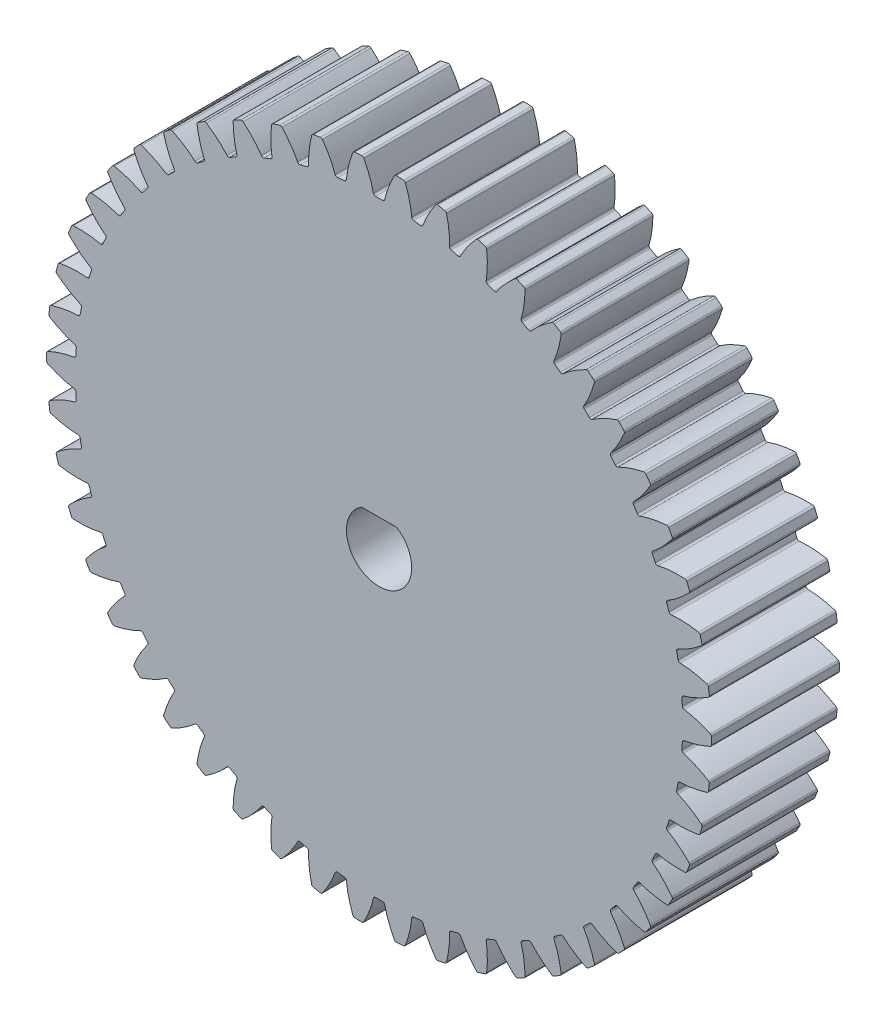
SolidWorks part; units mm, degrees
material "Alloy Steel"
ref_plane "Front" through (0, 0, 0) normal (0, 0, 1) x (1, 0, 0)
ref_plane "Top" through (0, 0, 0) normal (0, 1, 0) x (1, 0, 0)
ref_plane "Right" through (0, 0, 0) normal (1, 0, 0) x (0, 0, -1)
sketch "Sketch1" plane through (0, 0, 0) normal (0, 0, 1) x (1, 0, 0)
  circle A0 centre (0, 0) radius 26
  dimension "OutsideDiameter" = 52
extrude "Boss-Extrude1" add sketch "Sketch1" along normal blind 10
sketch "Sketch3" plane through (0, 0, 0) normal (0, 0, 1) x (1, 0, 0)
  line L0 (0, 0) -> (43.7181, 0) construction
  line L2 (0, 0) -> (-0.3921, 23.7468) construction
  line L3 (0, 0) -> (0.3921, 23.7468) construction
  line L4 (0.3921, 23.7468) -> (0.3879, 23.4891) construction
  line L5 (0, 0) -> (0, 61.276) construction
  line L6 (-0.3921, 23.7468) -> (-0.3879, 23.4891) construction
  circle A0 centre (0, 0) radius 26 construction
  circle A1 centre (0, 0) radius 25 construction
  circle A2 centre (0, 0) radius 23.4923 construction
  arc A3 (0.3921, 23.7468) -> (-0.3921, 23.7468) centre (0, 0) ccw construction
  arc A5 (1.2454, 25.9702) -> (-1.2454, 25.9702) centre (0, 0) ccw
  spline S0 degree 4 poles (-0.3879, 23.4891) (-0.388, 23.493) (-0.3884, 23.504) (-0.3897, 23.5247) (-0.3924, 23.5584) (-0.3969, 23.6014) (-0.4038, 23.6569) (-0.4135, 23.7223) (-0.4257, 23.7941) (-0.4406, 23.8721) (-0.4569, 23.9499) (-0.4746, 24.0275) (-0.4935, 24.1047) (-0.5179, 24.1981) (-0.5491, 24.3101) (-0.5886, 24.4407) (-0.6369, 24.5888) (-0.6899, 24.7394) (-0.7452, 24.8875) (-0.8046, 25.0368) (-0.8646, 25.1811) (-0.9305, 25.3308) (-0.9933, 25.4688) (-1.0677, 25.6231) (-1.1289, 25.7476) (-1.2139, 25.9114) (-1.2654, 26.008) (-1.3272, 26.121) (-1.3555, 26.1712) (-1.3728, 26.202) knots 0 0 0 0 0 0.005377 0.015084 0.028532 0.04661 0.064855 0.092111 0.119476 0.146842 0.174209 0.201575 0.228941 0.256307 0.307035 0.361767 0.4165 0.471232 0.525964 0.580697 0.635429 0.690161 0.744894 0.799626 0.854358 0.909091 0.954545 1 1 1 1 1 construction
  spline S1 degree 4 poles (-0.3879, 23.4891) (-0.388, 23.493) (-0.3884, 23.504) (-0.3897, 23.5247) (-0.3924, 23.5584) (-0.3969, 23.6014) (-0.4038, 23.6569) (-0.4135, 23.7223) (-0.4257, 23.7941) (-0.4406, 23.8721) (-0.4569, 23.9499) (-0.4746, 24.0275) (-0.4935, 24.1047) (-0.5179, 24.1981) (-0.5491, 24.3101) (-0.5886, 24.4407) (-0.6369, 24.5888) (-0.6899, 24.7394) (-0.7452, 24.8875) (-0.8046, 25.0368) (-0.8646, 25.1811) (-0.9305, 25.3308) (-0.9933, 25.4688) (-1.0677, 25.6231) (-1.1289, 25.7476) (-1.1955, 25.8759) (-1.2284, 25.9383) (-1.2454, 25.9702) knots 0 0 0 0 0 0.005377 0.015084 0.028532 0.04661 0.064855 0.092111 0.119476 0.146842 0.174209 0.201575 0.228941 0.256307 0.307035 0.361767 0.4165 0.471232 0.525964 0.580697 0.635429 0.690161 0.744894 0.799626 0.854358 0.909091 0.909091 0.909091 0.909091 0.909091
  spline S2 degree 4 poles (0.3879, 23.4891) (0.388, 23.493) (0.3884, 23.504) (0.3897, 23.5247) (0.3924, 23.5584) (0.3969, 23.6014) (0.4038, 23.6569) (0.4135, 23.7223) (0.4257, 23.7941) (0.4406, 23.8721) (0.4569, 23.9499) (0.4746, 24.0275) (0.4935, 24.1047) (0.5179, 24.1981) (0.5491, 24.3101) (0.5886, 24.4407) (0.6369, 24.5888) (0.6899, 24.7394) (0.7452, 24.8875) (0.8046, 25.0368) (0.8646, 25.1811) (0.9305, 25.3308) (0.9933, 25.4688) (1.0677, 25.6231) (1.1289, 25.7476) (1.2139, 25.9114) (1.2654, 26.008) (1.3272, 26.121) (1.3555, 26.1712) (1.3728, 26.202) knots 0 0 0 0 0 0.005377 0.015084 0.028532 0.04661 0.064855 0.092111 0.119476 0.146842 0.174209 0.201575 0.228941 0.256307 0.307035 0.361767 0.4165 0.471232 0.525964 0.580697 0.635429 0.690161 0.744894 0.799626 0.854358 0.909091 0.954545 1 1 1 1 1 construction
  spline S3 degree 4 poles (0.3879, 23.4891) (0.388, 23.493) (0.3884, 23.504) (0.3897, 23.5247) (0.3924, 23.5584) (0.3969, 23.6014) (0.4038, 23.6569) (0.4135, 23.7223) (0.4257, 23.7941) (0.4406, 23.8721) (0.4569, 23.9499) (0.4746, 24.0275) (0.4935, 24.1047) (0.5179, 24.1981) (0.5491, 24.3101) (0.5886, 24.4407) (0.6369, 24.5888) (0.6899, 24.7394) (0.7452, 24.8875) (0.8046, 25.0368) (0.8646, 25.1811) (0.9305, 25.3308) (0.9933, 25.4688) (1.0677, 25.6231) (1.1289, 25.7476) (1.1955, 25.8759) (1.2284, 25.9383) (1.2454, 25.9702) knots 0 0 0 0 0 0.005377 0.015084 0.028532 0.04661 0.064855 0.092111 0.119476 0.146842 0.174209 0.201575 0.228941 0.256307 0.307035 0.361767 0.4165 0.471232 0.525964 0.580697 0.635429 0.690161 0.744894 0.799626 0.854358 0.909091 0.909091 0.909091 0.909091 0.909091
  point P0 (0, 23.75)
  dimension "OutsideDiameter" = 52
  dimension "PitchCircle" = 50
  dimension "BaseCircle" = 46.9846
  dimension "DedendumCircle" = 47.5
sketch "DCLTBC" [suppressed] plane through (0, 0, 0) normal (0, 0, 1) x (1, 0, 0)
  line L0 (0, 0) -> (41.04, 0) construction
  line L1 (-0.539, 11.2371) -> (-0.5627, 11.7327) construction
  line L2 (0.539, 11.2371) -> (0.5627, 11.7327) construction
  line L3 (-0.539, 11.2371) -> (-0.5627, 11.7327)
  line L4 (0.539, 11.2371) -> (0.5627, 11.7327)
  line L5 (0, 0) -> (0, 104.9356) construction
  circle A0 centre (0, 0) radius 13.5
  circle A1 centre (0, 0) radius 12.5 construction
  circle A2 centre (0, 0) radius 11.7462 construction
  arc A3 (0.539, 11.2371) -> (-0.539, 11.2371) centre (0, 0) ccw construction
  arc A4 (0.539, 11.2371) -> (-0.539, 11.2371) centre (0, 0) ccw
  spline S0 degree 4 poles (-1995.7925, -124.0386) (-18.637, 9.6549) (-0.7482, 10.902) (-0.5144, 11.3546) (-0.568, 11.7819) (-0.5727, 11.8124) (-0.5797, 11.8517) (-0.5892, 11.8979) (-0.601, 11.9485) (-0.6152, 12.0034) (-0.6307, 12.0579) (-0.6473, 12.1122) (-0.6648, 12.1662) (-0.6873, 12.2313) (-0.716, 12.3091) (-0.752, 12.3996) (-0.7958, 12.5017) (-0.8436, 12.6052) (-0.8931, 12.7065) (-0.9461, 12.8082) (-0.9995, 12.9061) (-1.0579, 13.0071) (-1.1133, 13.1) (-1.1787, 13.2033) (-1.5156, 13.7241) (-2.9947, 15.6922) (22.2491, -20.3107) (-1154.5903, 1647.3833) knots -0.784355 -0.784355 -0.784355 -0.784355 -0.784355 0.005377 0.015084 0.028532 0.04661 0.064855 0.092111 0.119476 0.146842 0.174209 0.201575 0.228941 0.256307 0.307035 0.361767 0.4165 0.471232 0.525964 0.580697 0.635429 0.690161 0.744894 0.799626 0.854358 2.062408 2.062408 2.062408 2.062408 2.062408 only from (-0.5627, 11.7327) to (-1.3344, 13.4339) construction
  spline S1 degree 4 poles (1995.7925, -124.0386) (18.637, 9.6549) (0.7482, 10.902) (0.5144, 11.3546) (0.568, 11.7819) (0.5727, 11.8124) (0.5797, 11.8517) (0.5892, 11.8979) (0.601, 11.9485) (0.6152, 12.0034) (0.6307, 12.0579) (0.6473, 12.1122) (0.6648, 12.1662) (0.6873, 12.2313) (0.716, 12.3091) (0.752, 12.3996) (0.7958, 12.5017) (0.8436, 12.6052) (0.8931, 12.7065) (0.9461, 12.8082) (0.9995, 12.9061) (1.0579, 13.0071) (1.1133, 13.1) (1.1787, 13.2033) (1.5156, 13.7241) (2.9947, 15.6922) (-22.2491, -20.3107) (1154.5903, 1647.3833) knots -0.784355 -0.784355 -0.784355 -0.784355 -0.784355 0.005377 0.015084 0.028532 0.04661 0.064855 0.092111 0.119476 0.146842 0.174209 0.201575 0.228941 0.256307 0.307035 0.361767 0.4165 0.471232 0.525964 0.580697 0.635429 0.690161 0.744894 0.799626 0.854358 2.062408 2.062408 2.062408 2.062408 2.062408 only from (0.5627, 11.7327) to (1.3344, 13.4339) construction
  spline S2 degree 4 poles (-0.5627, 11.7327) (-0.5629, 11.7355) (-0.5635, 11.7432) (-0.565, 11.758) (-0.568, 11.7819) (-0.5727, 11.8124) (-0.5797, 11.8517) (-0.5892, 11.8979) (-0.601, 11.9485) (-0.6152, 12.0034) (-0.6307, 12.0579) (-0.6473, 12.1122) (-0.6648, 12.1662) (-0.6873, 12.2313) (-0.716, 12.3091) (-0.752, 12.3996) (-0.7958, 12.5017) (-0.8436, 12.6052) (-0.8931, 12.7065) (-0.9461, 12.8082) (-0.9995, 12.9061) (-1.0579, 13.0071) (-1.1133, 13.1) (-1.1787, 13.2033) (-1.2325, 13.2864) (-1.2907, 13.3715) (-1.3195, 13.4128) (-1.3344, 13.4339) knots 0 0 0 0 0 0.005377 0.015084 0.028532 0.04661 0.064855 0.092111 0.119476 0.146842 0.174209 0.201575 0.228941 0.256307 0.307035 0.361767 0.4165 0.471232 0.525964 0.580697 0.635429 0.690161 0.744894 0.799626 0.854358 0.909091 0.909091 0.909091 0.909091 0.909091
  spline S3 degree 4 poles (0.5627, 11.7327) (0.5629, 11.7355) (0.5635, 11.7432) (0.565, 11.758) (0.568, 11.7819) (0.5727, 11.8124) (0.5797, 11.8517) (0.5892, 11.8979) (0.601, 11.9485) (0.6152, 12.0034) (0.6307, 12.0579) (0.6473, 12.1122) (0.6648, 12.1662) (0.6873, 12.2313) (0.716, 12.3091) (0.752, 12.3996) (0.7958, 12.5017) (0.8436, 12.6052) (0.8931, 12.7065) (0.9461, 12.8082) (0.9995, 12.9061) (1.0579, 13.0071) (1.1133, 13.1) (1.1787, 13.2033) (1.2325, 13.2864) (1.2907, 13.3715) (1.3195, 13.4128) (1.3344, 13.4339) knots 0 0 0 0 0 0.005377 0.015084 0.028532 0.04661 0.064855 0.092111 0.119476 0.146842 0.174209 0.201575 0.228941 0.256307 0.307035 0.361767 0.4165 0.471232 0.525964 0.580697 0.635429 0.690161 0.744894 0.799626 0.854358 0.909091 0.909091 0.909091 0.909091 0.909091
  dimension "OutsideDiameter" = 52
  dimension "PitchCircle" = 50
  dimension "BaseCircle" = 46.9846
extrude "Cut-Extrude-DCLTBC" [suppressed] cut sketch "DCLTBC" along normal through all
fillet "Fillet-Tip-DCLTBC" [suppressed] radius 0.1678
fillet "Fillet-Root-DCLTBC" [suppressed] radius 0.3355
pattern_circular "CirPattern-DCLTBC" [suppressed] count 50 over 360 of bodies 111
sketch "DCGTBC" plane through (0, 0, 0) normal (0, 0, 1) x (1, 0, 0)
  line L0 (0, 0) -> (41.04, 0) construction
  line L1 (-23.6596, 2.0699) -> (0, 0) construction
  line L2 (0, 0) -> (23.6596, 2.0699) construction
  line L3 (0, 0) -> (-16.5124, 0)
  line L5 (0, 0) -> (0, 104.9356) construction
  circle A0 centre (0, 0) radius 26
  circle A1 centre (0, 0) radius 25 construction
  circle A2 centre (0, 0) radius 23.4923 construction
  arc A3 (0.3921, 23.7468) -> (-0.3921, 23.7468) centre (0, 0) ccw construction
  arc A11 (23.6596, 2.0699) -> (-23.6596, 2.0699) centre (0, 0) ccw
  spline S4 degree 4 poles (999.4864, -18.7848) (11.7157, 21.9438) (0.5361, 22.5725) (0.3526, 23.0676) (0.3924, 23.5584) (0.3969, 23.6014) (0.4038, 23.6569) (0.4135, 23.7223) (0.4257, 23.7941) (0.4406, 23.8721) (0.4569, 23.9499) (0.4746, 24.0275) (0.4935, 24.1047) (0.5179, 24.1981) (0.5491, 24.3101) (0.5886, 24.4407) (0.6369, 24.5888) (0.6899, 24.7394) (0.7452, 24.8875) (0.8046, 25.0368) (0.8646, 25.1811) (0.9305, 25.3308) (0.9933, 25.4688) (1.0677, 25.6231) (1.3761, 26.2503) (2.5138, 28.2725) (-11.1356, 2.527) (472.7395, 907.8123) knots -0.631302 -0.631302 -0.631302 -0.631302 -0.631302 0.005377 0.015084 0.028532 0.04661 0.064855 0.092111 0.119476 0.146842 0.174209 0.201575 0.228941 0.256307 0.307035 0.361767 0.4165 0.471232 0.525964 0.580697 0.635429 0.690161 0.744894 0.799626 0.854358 1.793522 1.793522 1.793522 1.793522 1.793522 only from (0.3879, 23.4891) to (1.2454, 25.9702) construction
  spline S5 degree 4 poles (-999.4864, -18.7848) (-11.7157, 21.9438) (-0.5361, 22.5725) (-0.3526, 23.0676) (-0.3924, 23.5584) (-0.3969, 23.6014) (-0.4038, 23.6569) (-0.4135, 23.7223) (-0.4257, 23.7941) (-0.4406, 23.8721) (-0.4569, 23.9499) (-0.4746, 24.0275) (-0.4935, 24.1047) (-0.5179, 24.1981) (-0.5491, 24.3101) (-0.5886, 24.4407) (-0.6369, 24.5888) (-0.6899, 24.7394) (-0.7452, 24.8875) (-0.8046, 25.0368) (-0.8646, 25.1811) (-0.9305, 25.3308) (-0.9933, 25.4688) (-1.0677, 25.6231) (-1.3761, 26.2503) (-2.5138, 28.2725) (11.1356, 2.527) (-472.7395, 907.8123) knots -0.631302 -0.631302 -0.631302 -0.631302 -0.631302 0.005377 0.015084 0.028532 0.04661 0.064855 0.092111 0.119476 0.146842 0.174209 0.201575 0.228941 0.256307 0.307035 0.361767 0.4165 0.471232 0.525964 0.580697 0.635429 0.690161 0.744894 0.799626 0.854358 1.793522 1.793522 1.793522 1.793522 1.793522 only from (-0.3879, 23.4891) to (-1.2454, 25.9702) construction
  spline S6 degree 4 poles (0.3879, 23.4891) (0.388, 23.493) (0.3884, 23.504) (0.3897, 23.5247) (0.3924, 23.5584) (0.3969, 23.6014) (0.4038, 23.6569) (0.4135, 23.7223) (0.4257, 23.7941) (0.4406, 23.8721) (0.4569, 23.9499) (0.4746, 24.0275) (0.4935, 24.1047) (0.5179, 24.1981) (0.5491, 24.3101) (0.5886, 24.4407) (0.6369, 24.5888) (0.6899, 24.7394) (0.7452, 24.8875) (0.8046, 25.0368) (0.8646, 25.1811) (0.9305, 25.3308) (0.9933, 25.4688) (1.0677, 25.6231) (1.1289, 25.7476) (1.1955, 25.8759) (1.2284, 25.9383) (1.2454, 25.9702) knots 0 0 0 0 0 0.005377 0.015084 0.028532 0.04661 0.064855 0.092111 0.119476 0.146842 0.174209 0.201575 0.228941 0.256307 0.307035 0.361767 0.4165 0.471232 0.525964 0.580697 0.635429 0.690161 0.744894 0.799626 0.854358 0.909091 0.909091 0.909091 0.909091 0.909091
  spline S7 degree 4 poles (-0.3879, 23.4891) (-0.388, 23.493) (-0.3884, 23.504) (-0.3897, 23.5247) (-0.3924, 23.5584) (-0.3969, 23.6014) (-0.4038, 23.6569) (-0.4135, 23.7223) (-0.4257, 23.7941) (-0.4406, 23.8721) (-0.4569, 23.9499) (-0.4746, 24.0275) (-0.4935, 24.1047) (-0.5179, 24.1981) (-0.5491, 24.3101) (-0.5886, 24.4407) (-0.6369, 24.5888) (-0.6899, 24.7394) (-0.7452, 24.8875) (-0.8046, 25.0368) (-0.8646, 25.1811) (-0.9305, 25.3308) (-0.9933, 25.4688) (-1.0677, 25.6231) (-1.1289, 25.7476) (-1.1955, 25.8759) (-1.2284, 25.9383) (-1.2454, 25.9702) knots 0 0 0 0 0 0.005377 0.015084 0.028532 0.04661 0.064855 0.092111 0.119476 0.146842 0.174209 0.201575 0.228941 0.256307 0.307035 0.361767 0.4165 0.471232 0.525964 0.580697 0.635429 0.690161 0.744894 0.799626 0.854358 0.909091 0.909091 0.909091 0.909091 0.909091
  dimension "D1" = 5
  dimension "D2" = 5
  dimension "OutsideDiameter" = 52
  dimension "PitchCircle" = 50
  dimension "BaseCircle" = 46.9846
extrude "Cut-Extrude-DCGTBC" cut sketch "DCGTBC" along normal through all contours A0 A11 region at (0, 25.0744, 0)
fillet "Fillet-Tip-DCGTBC" radius 0.1678 4 edges at (1.2454, 25.9702, 5) (-1.2454, 25.9702, 5) (0.4177, 23.7463, 5) (-0.4177, 23.7463, 5)
pattern_circular "CirPattern-DCGTBC" count 50 over 360 about axis through (0, 0, 10) along (0, 0, 1) of "Cut-Extrude-DCGTBC", "Fillet-Tip-DCGTBC"
sketch "Sketch5" [suppressed] plane through (0, 0, 10) normal (0, 0, 1) x (1, 0, 0)
  circle A0 centre (0, 0) radius 11.25
  arc A1 (0.2133, 11.248) -> (-0.2133, 11.248) centre (0, 0) ccw construction
extrude "Boss-Extrude2" [suppressed] add sketch "Sketch5" along normal blind 7
sketch "Sketch6" plane through (0, 0, 0) normal (0, 0, -1) x (-1, 0, 0)
  line L0 (-1.3711, 2.15) -> (1.3711, 2.15)
  arc A0 (-1.3711, 2.15) -> (1.3711, 2.15) centre (0, 0) ccw
  dimension "D1" = 5.1
  dimension "D2" = 2.15
extrude "Cut-Extrude1" cut sketch "Sketch6" against normal through all both and the other way through all
sketch "Sketch7" plane through (0, 0, 0) normal (0, 0, -1) x (-1, 0, 0)
  circle A0 centre (0, 0) radius 25
  dimension "D1" = 50
sketch "Sketch8" plane through (0, 0, 10) normal (0, 0, 1) x (1, 0, 0)
  circle A0 centre (0, 0) radius 25
  dimension "D1" = 50
equation "\"DiametralPitch\"= 25.4 / 1 'Diametral Pitch"
equation "\"NumTeeth\" = 50'Number of Teeth"
equation "\"PressureAngle\"= 20deg'Pressure Angle"
equation "\"Addendum\"= 1 / \"DiametralPitch\"'Addendum"
equation "\"Dedendum\"= 1.25 / \"DiametralPitch\"'Dedendum"
equation "\"WorkingDepth\"= 2 / \"DiametralPitch\"'Working Depth - here for REF (Not used in building model)"
equation "\"WholeDepth\"= 2.25 / \"DiametralPitch\"'Whole Depth - here for REF (Not used in building model)"
equation "\"Clearance\"= .25 / \"DiametralPitch\"'Clearance"
equation "\"CircularPitch\"= pi / \"DiametralPitch\"'Circular Pitch - here for REF (Not used in building model)"
equation "\"PitchCircle\"= \"NumTeeth\" / \"DiametralPitch\"'Pitch Circle - or - Pitch Diameter"
equation "\"OutsideDiameter\"= ( \"NumTeeth\" + 2 ) / \"DiametralPitch\"'Outside Diameter"
equation "\"Fillet_Root\"= \"Clearance\" * cos ( \"PressureAngle\" ) * tan ( ( 90 + \"PressureAngle\" ) / 2 ) 'Fillet Root"
equation "\"AddendumCircle\"= \"PitchCircle\" + ( 2 * \"Addendum\" )'Addendum Circle - or - Addendum Diameter"
equation "\"DedendumCircle\"= \"PitchCircle\" - ( 2 * \"Dedendum\" )'Dedendum Circle - or - Dedendum Diameter"
equation "\"BaseCircle\"= \"PitchCircle\" * cos ( \"PressureAngle\" )'Base Circle - Base Diameter"
equation "\"PitchAngle\"= 360deg / \"NumTeeth\"'Pitch Angle"
equation "\"Alpha\"= sqr ( \"PitchCircle\" ^ 2 - \"BaseCircle\" ^ 2 ) / \"BaseCircle\" * 180 / PI - \"PressureAngle\"'Alpha - Used for Calculating Beta"
equation "\"Beta\"= ( \"PitchAngle\" / 4 - ( \"Alpha\" - 90 ) )'Beta - Used in definition of the parameters for the parametric equation driven curve"
equation "\"Gamma\"= ( \"PitchAngle\" / 4 - ( \"Alpha\" + 90 ) )'Gamma - Used in definition of the parameters for the parametric equation driven curve"
equation "\"Phi\"= sqr ( ( \"AddendumCircle\" / 2 ) ^ 2 - ( \"BaseCircle\" / 2 ) ^ 2 ) / ( \"BaseCircle\" / 2 )'Phi - Used in definition of the parameters for the parametric equation driven curve"
equation "\"DCGTBC\"= iif ( \"DedendumCircle\" > \"BaseCircle\" , \"unsuppressed\" , \"suppressed\" )'if Dedendum Circle IS GREATER THAN BaseCircle THEN UnsuppressORSuppress FEATURE"
equation "\"DCLTBC\"= iif ( \"DedendumCircle\" - .002 > \"BaseCircle\" , \"suppressed\" , \"unsuppressed\" )'if Dedendum Circle - .002 IS GREATER THAN BaseCircle THEN SuppressORUnsuppress FEATURE"
equation "\"Cut-Extrude-DCGTBC\"= iif ( \"DedendumCircle\" > \"BaseCircle\" , \"unsuppressed\" , \"suppressed\" )'if Dedendum Circle IS GREATER THAN BaseCircle THEN UnsuppressORSuppress FEATURE"
equation "\"Cut-Extrude-DCLTBC\"= iif ( \"DedendumCircle\" - .002 > \"BaseCircle\" , \"suppressed\" , \"unsuppressed\" )'if Dedendum Circle - .002 IS GREATER THAN BaseCircle THEN SuppressORUnsuppress FEATURE"
equation "\"CirPattern-DCGTBC\"= iif ( \"DedendumCircle\" > \"BaseCircle\" , \"unsuppressed\" , \"suppressed\" )'if Dedendum Circle IS GREATER THAN BaseCircle THEN UnsuppressORSuppress FEATURE"
equation "\"CirPattern-DCLTBC\"= iif ( \"DedendumCircle\" - .002 > \"BaseCircle\" , \"suppressed\" , \"unsuppressed\" )'if Dedendum Circle - .002 IS GREATER THAN BaseCircle THEN SuppressORUnsuppress FEATURE"
equation "\"Fillet-Tip-DCGTBC\"= iif ( \"DedendumCircle\" > \"BaseCircle\" , \"unsuppressed\" , \"suppressed\" )'if Dedendum Circle IS GREATER THAN BaseCircle THEN UnsuppressORSuppress FEATURE"
equation "\"Fillet-Tip-DCLTBC\"= iif ( \"DedendumCircle\" - .002 > \"BaseCircle\" , \"suppressed\" , \"unsuppressed\" )'if Dedendum Circle - .002 IS GREATER THAN BaseCircle THEN SuppressORUnsuppress FEATURE"
equation "\"Fillet-Root-DCLTBC\"= iif ( \"DedendumCircle\" - .002 > \"BaseCircle\" , \"suppressed\" , \"unsuppressed\" )'if Dedendum Circle - .002 IS GREATER THAN BaseCircle THEN SuppressORUnsuppress FEATURE"
equation "\"D1@CirPattern-DCGTBC\"= \"NumTeeth\"'Number of Teeth"
equation "\"D1@CirPattern-DCLTBC\"= \"NumTeeth\"'Number of Teeth"
equation "\"D1@Fillet-Tip-DCGTBC\"= \"Fillet_Root\" / 2 'Tip Rad For Large No of Teeth"
equation "\"D1@Fillet-Tip-DCLTBC\"=\"Fillet_Root\" / 2'Tip Rad For Small No of Teeth"
equation "\"D1@Fillet-Root-DCLTBC\"= \"Fillet_Root\"'Fillet Root"
equation "\"D2@Sketch6\"=\"D1@Sketch6\"/2-0.4mm"
